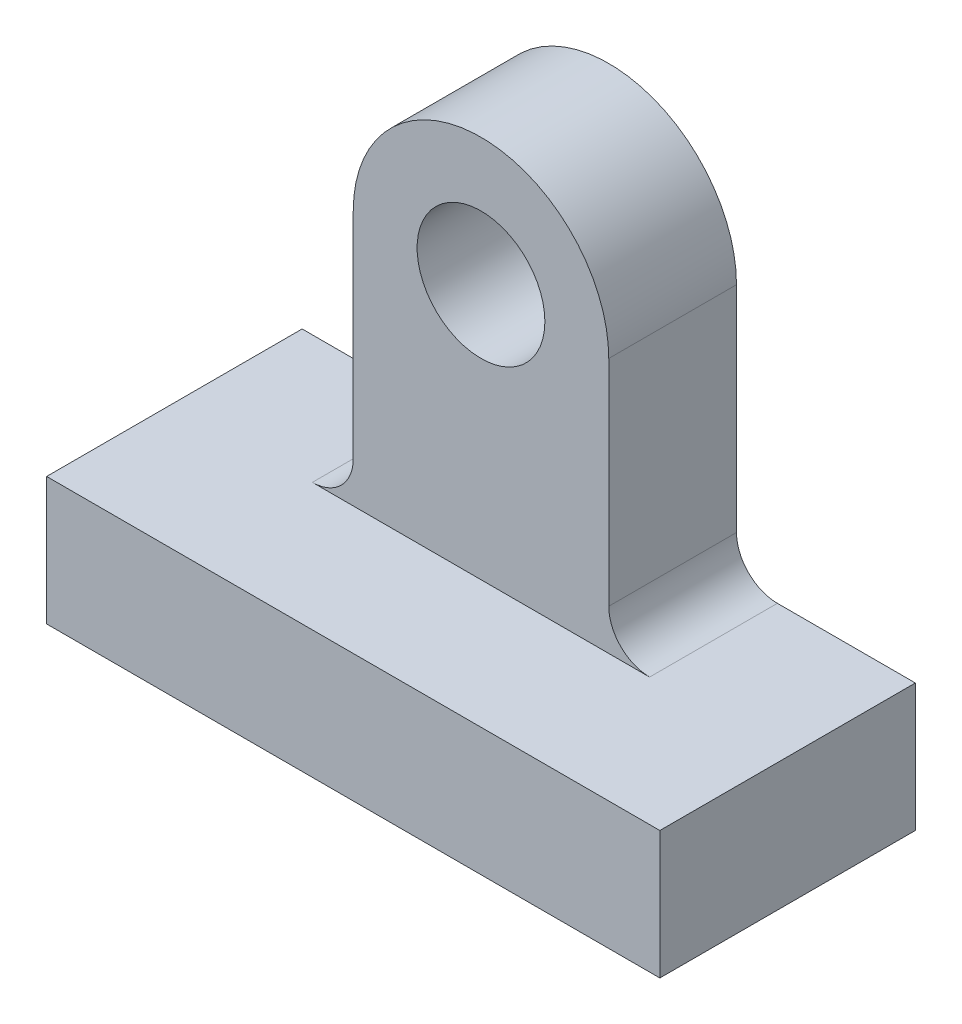
SolidWorks part; units mm, degrees
ref_plane "Front Plane" through (0, 0, 0) normal (0, 0, 1) x (1, 0, 0)
ref_plane "Top Plane" through (0, 0, 0) normal (0, 1, 0) x (1, 0, 0)
ref_plane "Right Plane" through (0, 0, 0) normal (1, 0, 0) x (0, 0, -1)
sketch "Sketch1" plane through (0, 0, 0) normal (0, 1, 0) x (1, 0, 0)
  line L6 (-60, -25) -> (60, -25)
  line L12 (-60, -25) -> (-60, 25)
  line L13 (-60, 25) -> (60, 25)
  line L14 (60, -25) -> (60, 25)
  line L15 (-60, -25) -> (60, 25) construction
  line L16 (-60, 25) -> (60, -25) construction
  point P0 (0, 0)
  dimension "D2" = 50
  dimension "D1" = 120
extrude "Boss-Extrude3" add sketch "Sketch1" along normal blind 25
sketch "Sketch2" plane through (0, 25, 0) normal (0, 1, 0) x (1, 0, 0)
  line L0 (0, 25) -> (0, -25) construction
  line L1 (60, 25) -> (-60, 25) construction
  line L2 (-60, -25) -> (60, -25) construction
  line L3 (-25, 25) -> (-25, 0)
  line L4 (-25, 25) -> (25, 25)
  line L6 (-25, 0) -> (25, 0)
  line L7 (25, 25) -> (25, 0)
  point P11 (0, 0)
  dimension "D1" = 25
  dimension "D2" = 25
extrude "Boss-Extrude4" add sketch "Sketch2" along normal blind 75 contours L3 L6 L7 L4
sketch "Sketch3" plane through (0, 0, 0) normal (0, 0, 1) x (1, 0, 0)
  line L0 (0, 100) -> (0, 70.2956) construction
  line L1 (-25, 100) -> (25, 100) construction
  line L2 (0, 100) -> (0, 75)
  line L3 (25, 100) -> (25, 25) construction
  line L4 (-25, 100) -> (-25, 25) construction
  line L5 (-25, 75) -> (-25, 100)
  line L7 (25, 100) -> (25, 75)
  line L8 (-25, 100) -> (25, 100)
  circle A0 centre (0, 75) radius 12.5
  arc A1 (25, 75) -> (-25, 75) centre (0, 75) ccw
  line M2 (25, 25) -> (25, 100)
  line M3 (25, 100) -> (-25, 100)
  line M4 (-25, 100) -> (-25, 25)
  dimension "D1" = 25
  dimension "D2" = 25
extrude "Cut-Extrude2" cut sketch "Sketch3" against normal through all contours A1 M3 M4 | A1 M2 M3 | A0 region at (8.5888, 83.5888, 0) region at (-19.4158, 94.4158, 0) region at (19.4158, 94.4158, 0)
fillet "Fillet1" radius 8 2 edges at (-25, 25, -12.5) (25, 25, -12.5)
